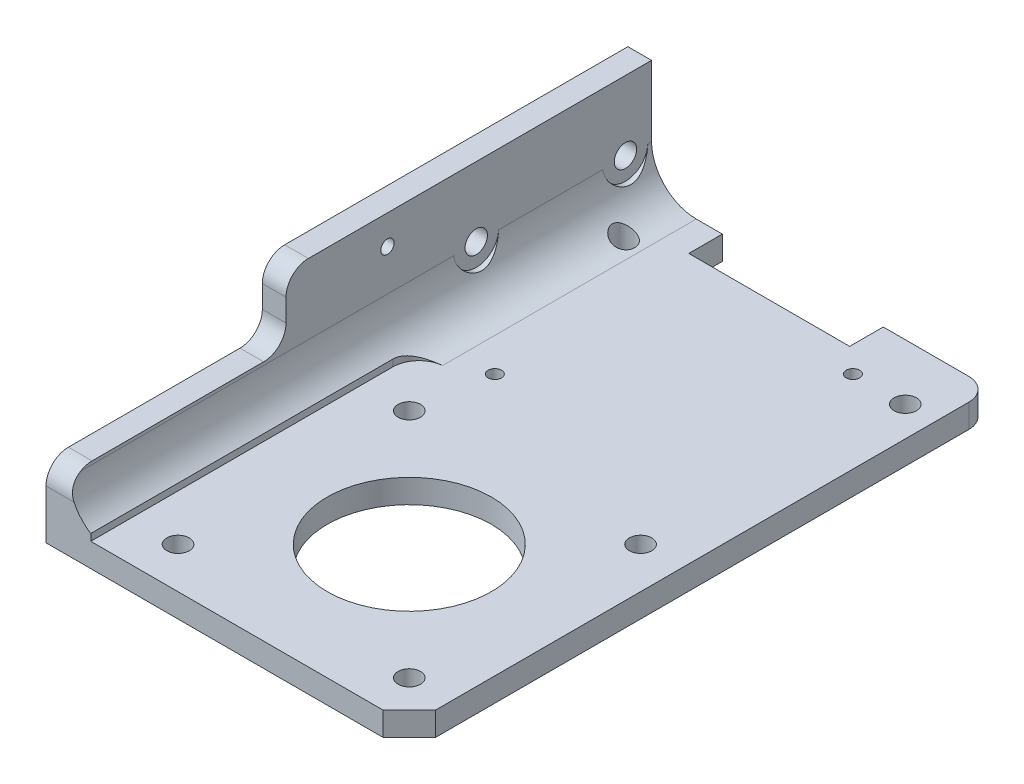
SolidWorks part; units mm, degrees
ref_plane "Front Plane" through (0, 0, 0) normal (0, 0, 1) x (1, 0, 0)
ref_plane "Top Plane" through (0, 0, 0) normal (0, 1, 0) x (1, 0, 0)
ref_plane "Right Plane" through (0, 0, 0) normal (1, 0, 0) x (0, 0, -1)
sketch "Sketch1" plane through (0, 0, 0) normal (0, 0, 1) x (1, 0, 0)
  line L0 (0, 0) -> (0, 18.6)
  line L1 (0, 0) -> (48.7, 0)
  line L2 (3.175, 3.175) -> (48.7, 3.175)
  line L3 (3.175, 3.175) -> (3.175, 18.6)
  line L4 (0, 18.6) -> (3.175, 18.6)
  line L5 (48.7, 0) -> (48.7, 3.175)
  dimension "D1" = 18.6
  dimension "D2" = 48.7
  dimension "D3" = 3.175
extrude "Boss-Extrude1" add sketch "Sketch1" along normal blind 68.15
fillet "Fillet1" radius 6 1 edges at (3.175, 3.175, 34.075)
sketch "Sketch2" plane through (3.175, 0, 0) normal (1, 0, 0) x (0, 0, -1)
  circle A1 centre (-23.5, 9.3) radius 1.5
  circle A2 centre (0.9, 30.5) radius 1.5
  circle A3 centre (-3.5, 9.3) radius 1.5
  dimension "D1" = 3
  dimension "D2" = 3
extrude "Cut-Extrude1" cut sketch "Sketch2" against normal blind 10
sketch "Sketch5" plane through (0, 0, 68.15) normal (0, 0, 1) x (1, 0, 0)
  line L0 (0, 0) -> (0, 3.175)
  line L6 (0, 0) -> (48.7, 0)
  line L7 (48.7, 0) -> (48.7, 3.175)
  line L8 (48.7, 3.175) -> (9.175, 3.175)
  line L9 (3.175, 9.175) -> (3.175, 18.6)
  line L10 (3.175, 18.6) -> (0, 18.6)
  line L11 (0, 18.6) -> (0, 0)
  line L12 (0, 0) -> (48.7, 0)
  line L13 (48.7, 0) -> (48.7, 3.175)
  line L14 (48.7, 3.175) -> (0, 3.175)
  arc A1 (3.175, 9.175) -> (9.175, 3.175) centre (9.175, 9.175) ccw
  dimension "D1" = 0
extrude "Boss-Extrude2" add sketch "Sketch5" along normal blind 9.85
sketch "Sketch10" plane through (0, 0, 68.15) normal (0, 0, 1) x (1, 0, 0)
  line L4 (0, 3.175) -> (9.175, 3.175)
  line L5 (3.175, 9.175) -> (3.175, 18.6)
  line L6 (3.175, 18.6) -> (0, 18.6)
  line L7 (0, 18.6) -> (0, 3.175)
  line L8 (0, 3.175) -> (9.175, 3.175)
  line L9 (3.175, 9.175) -> (3.175, 18.6)
  line L10 (3.175, 18.6) -> (0, 18.6)
  line L11 (0, 18.6) -> (0, 3.175)
  arc A1 (3.175, 9.175) -> (9.175, 3.175) centre (9.175, 9.175) ccw
  arc A2 (3.175, 9.175) -> (9.175, 3.175) centre (9.175, 9.175) ccw
  dimension "D1" = 0
extrude "Boss-Extrude5" add sketch "Sketch10" along normal up to surface (9.85 mm away) up to face at (24.35, 1.5875, 78)
sketch "Sketch15" plane through (3.175, 0, 0) normal (1, 0, 0) x (0, 0, -1)
  circle A0 centre (-3.5, 9.3) radius 3
  circle A1 centre (-23.5, 9.3) radius 3
  dimension "D1" = 6
extrude "Cut-Extrude4" cut sketch "Sketch15" along normal blind 3
sketch "Sketch16" plane through (0, 0, 0) normal (0, -1, 0) x (1, 0, 0)
  line L0 (48.7, 78) -> (48.7, 74.4645)
  line L1 (48.7, 78) -> (48.7, 0) construction
  line L2 (48.7, 74.4645) -> (45.1645, 78)
  line L3 (0, 78) -> (48.7, 78) construction
  line L4 (45.1645, 78) -> (48.7, 78)
  dimension "D1" = 5
extrude "Cut-Extrude5" cut sketch "Sketch16" against normal blind 4
sketch "Sketch17" plane through (0, 0, 0) normal (-1, 0, 0) x (0, 0, 1)
  line L0 (78, 9.6) -> (49, 9.6)
  line L2 (49, 9.6) -> (49, 18.6)
  line L3 (78, 18.6) -> (78, 0) construction
  line L5 (78, 18.6) -> (0, 18.6) construction
  line L6 (78, 9.6) -> (78, 18.6)
  line L7 (78, 18.6) -> (49, 18.6)
  dimension "D1" = 9
  dimension "D2" = 29
extrude "Cut-Extrude6" cut sketch "Sketch17" against normal blind 10
fillet "Fillet2" radius 3 4 edges at (1.5875, 18.6, 49) (1.5875, 9.6, 49) (1.5875, 9.6, 78) (48.7, 1.5875, 0)
sketch "Sketch18" plane through (0, 0, 0) normal (-1, 0, 0) x (0, 0, 1)
  circle A1 centre (35.4, 14.675) radius 0.9
  dimension "D1" = 1.8
extrude "Cut-Extrude7" cut sketch "Sketch18" against normal blind 4
sketch "Sketch19" plane through (0, 3.175, 0) normal (0, 1, 0) x (1, 0, 0)
  line L0 (12.2, -41.5) -> (43.2, -41.5) construction
  line L1 (27.7, -41.5) -> (27.7, -56.8771) construction
  circle A3 centre (43.2, -72.5) radius 1.5
  circle A4 centre (12.2, -41.5) radius 1.5
  circle A5 centre (43.2, -41.5) radius 1.5
  circle A6 centre (12.2, -72.5) radius 1.5
extrude "Cut-Extrude8" cut sketch "Sketch19" against normal blind 10
sketch "Sketch20" plane through (0, 0, 0) normal (0, -1, 0) x (1, 0, 0)
  circle A1 centre (27.7, 57) radius 11
  dimension "D1" = 22
extrude "Cut-Extrude9" cut sketch "Sketch20" against normal blind 10
sketch "Sketch21" plane through (0, 0, 78) normal (0, 0, 1) x (1, 0, 0)
  line L0 (0, 6.6) -> (0, 0) construction
  line L1 (6, 3.175) -> (11, 3.175)
  line L2 (6, 3.175) -> (6, 4.175)
  line L3 (6, 4.175) -> (11, 4.175)
  line L4 (11, 3.175) -> (11, 4.175)
  dimension "D1" = 5
  dimension "D2" = 1
  dimension "D3" = 6
extrude "Cut-Extrude10" cut sketch "Sketch21" against normal blind 44
fillet "Fillet3" radius 3.5 1 edges at (6, 3.6294, 34)
sketch "Sketch22" plane through (0, 0, 0) normal (0, -1, 0) x (1, 0, 0)
  circle A2 centre (13.665, 31.5) radius 0.9
  circle A3 centre (37.665, 7.5) radius 0.9
extrude "Cut-Extrude11" cut sketch "Sketch22" against normal blind 4
sketch "Sketch23" plane through (0, 0, 0) normal (0, -1, 0) x (1, 0, 0)
  line L0 (0, 0) -> (45.7, 0) construction
  line L1 (34.2362, 0) -> (12.665, 0)
  line L2 (34.2362, 0) -> (34.2362, 4.5)
  line L3 (34.2362, 4.5) -> (12.665, 4.5)
  line L4 (12.665, 0) -> (12.665, 4.5)
  line L5 (12.665, 4.5) -> (12.665, 28.2) construction
  line L7 (34.2362, 7.5) -> (34.2362, 4.5) construction
extrude "Cut-Extrude12" cut sketch "Sketch23" against normal blind 4
sketch "Sketch24" plane through (0, 0, 0) normal (0, -1, 0) x (1, 0, 0)
  circle A9 centre (6.92, 7.5) radius 1.5
  circle A10 centre (44.6825, 7.5) radius 1.5
extrude "Cut-Extrude13" cut sketch "Sketch24" against normal blind 6
